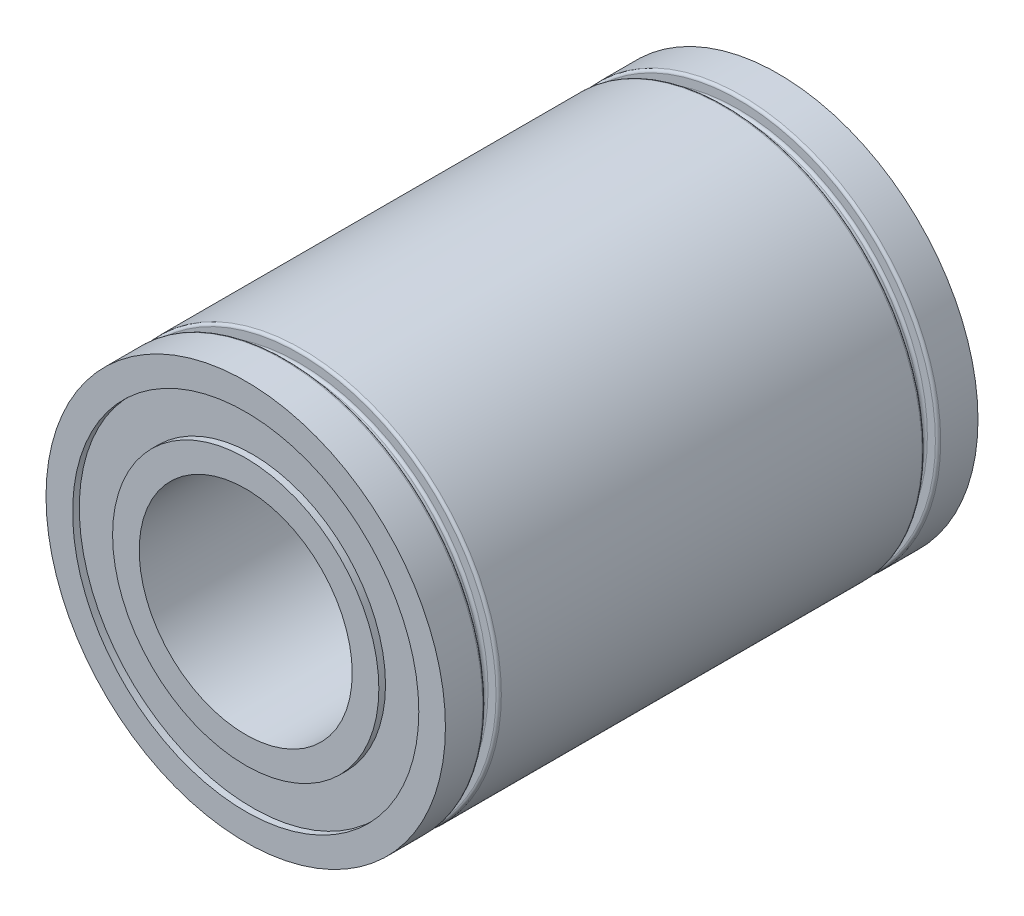
SolidWorks part; units mm, degrees
ref_plane "Front Plane" through (0, 0, 0) normal (0, 0, 1) x (1, 0, 0)
ref_plane "Top Plane" through (0, 0, 0) normal (0, 1, 0) x (1, 0, 0)
ref_plane "Right Plane" through (0, 0, 0) normal (1, 0, 0) x (0, 0, -1)
sketch "Sketch2" plane through (0, 0, 0) normal (0, 0, 1) x (1, 0, 0)
  circle A0 centre (0, 0) radius 4
  circle A1 centre (0, 0) radius 7.5
  circle A2 centre (0, 0) radius 5
  circle A3 centre (0, 0) radius 6.5
  dimension "D1" = 8
  dimension "D2" = 15
  dimension "D3" = 1
  dimension "D4" = 1.5
extrude "Boss-Extrude1" add sketch "Sketch2" along normal mid plane 20 contours A2 A0 | A1 A3 region at (-7.2879, 0, 0) region at (-4.8586, 0, 0)
extrude "Boss-Extrude2" add sketch "Sketch2<3>" along normal mid plane 19.5 separate body contours A3 A2 region at (-6.3162, 0, 0)
sketch "Sketch2<3>" plane through (0, 0, 0) normal (0, 0, 1) x (1, 0, 0) same geometry as "Sketch2"
sketch "Sketch3" plane through (0, 0, 0) normal (0, 1, 0) x (1, 0, 0)
  line L0 (0, 10) -> (0, -10) construction
  line L1 (7.5, 10) -> (-7.5, 10) construction
  line L2 (-7.5, -10) -> (7.5, -10) construction
  line L3 (0, -10) -> (0, 0) construction
  line L4 (0, 0) -> (-9.329, 0) construction
  line L5 (7.5, -10) -> (7.5, 10) construction
  line L6 (7, 8.5) -> (8, 8.5)
  line L7 (7, 8.5) -> (7, 8)
  line L8 (7, 8) -> (8, 8)
  line L9 (8, 8.5) -> (8, 8)
  line L10 (7, 8.5) -> (8, 8) construction
  line L11 (7, 8) -> (8, 8.5) construction
  line L12 (7, -8) -> (8, -8.5) construction
  line L13 (7, -8.5) -> (8, -8) construction
  line L14 (8, -8.5) -> (8, -8)
  line L15 (7, -8) -> (8, -8)
  line L16 (7, -8.5) -> (7, -8)
  line L17 (7, -8.5) -> (8, -8.5)
  point P9 (7.5, 8.25)
  point P20 (7.5, -8.25)
  dimension "D1" = 0.5
  dimension "D2" = 7
  dimension "D3" = 1.5
revolve "Cut-Revolve1" cut sketch "Sketch3" angle 360 about L0
fillet "Fillet1" radius 0.1 8 edges at (-7, 0, -8.5) (7.5, 0, -8.5) (-7, 0, -8) (-7.5, 0, -8) (-7, 0, 8.5) (-7, 0, 8) (7.5, 0, 8) (-7.5, 0, 8.5)
